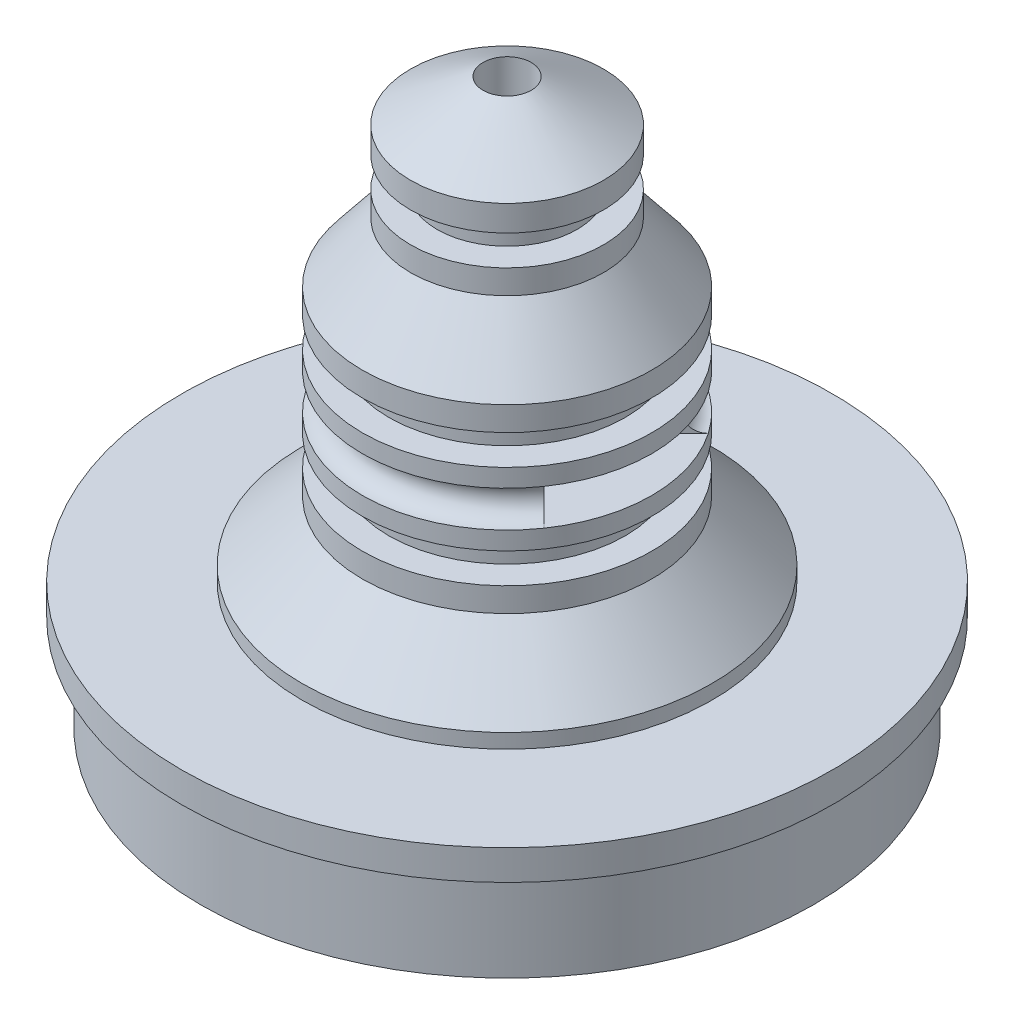
SolidWorks part; units mm, degrees
ref_plane "Спереди" through (0, 0, 0) normal (0, 0, 1) x (1, 0, 0)
ref_plane "Сверху" through (0, 0, 0) normal (0, 1, 0) x (1, 0, 0)
ref_plane "Справа" through (0, 0, 0) normal (1, 0, 0) x (0, 0, -1)
sketch "Эскиз1" plane through (0, 0, 0) normal (0, 0, 1) x (1, 0, 0)
  line L0 (0, 0) -> (0, 60) construction
  line L1 (17, 27) -> (17, 25.8)
  line L2 (2, 62.0979) -> (2, 15.3)
  line L6 (8, 56.5) -> (5.8, 56.5)
  line L7 (5.8, 56.5) -> (5.8, 54)
  line L8 (5.8, 54) -> (8, 54)
  line L10 (8, 58.6338) -> (8, 56.5)
  line L11 (8, 54) -> (8, 52)
  line L12 (8, 52) -> (12, 47)
  line L13 (12, 47) -> (12, 45)
  line L14 (12, 45) -> (9.8, 45)
  line L15 (9.8, 45) -> (9.8, 42.5)
  line L16 (9.8, 42.5) -> (12, 42.5)
  line L17 (12, 39.5) -> (9.0242, 39.5) construction
  line L18 (12, 42.5) -> (12, 41)
  line L19 (12, 36.5) -> (12, 38)
  line L20 (12, 34) -> (9.8, 34)
  line L21 (9.8, 34) -> (9.8, 36.5)
  line L22 (9.8, 36.5) -> (12, 36.5)
  line L23 (12, 34) -> (12, 32)
  line L24 (12, 32) -> (17, 27)
  line L29 (17, 25.8) -> (27, 25.8)
  line L33 (27, 25.8) -> (27, 23.3)
  line L34 (27, 23.3) -> (25.4, 23.3)
  line L35 (25.4, 23.3) -> (25.4, 15.3)
  line L36 (25.4, 15.3) -> (2, 15.3)
  line L37 (8, 58.6338) -> (2, 62.0979)
  arc A1 (12, 41) -> (12, 38) centre (12, 39.5) ccw
  point P22 (12, 41)
  dimension "D5" = 2.5
  dimension "D14" = 3
  dimension "D3" = 4
  dimension "D4" = 16
  dimension "D6" = 2
  dimension "D7" = 2.2
  dimension "D8" = 60
  dimension "D9" = 24
  dimension "D10" = 5
  dimension "D11" = 2.5
  dimension "D12" = 2.2
  dimension "D13" = 2
  dimension "D15" = 1.5
  dimension "D16" = 2
  dimension "D17" = 5
  dimension "D18" = 34
  dimension "D19" = 1.2
  dimension "D20" = 2.5
  dimension "D21" = 8
  dimension "D22" = 10
  dimension "D23" = 1.6
  dimension "D24" = 7.8
revolve "Повернуть1" add sketch "Эскиз1" angle 360 about L0 reverse direction yes
sketch "Эскиз3" plane through (0, 15.3, 0) normal (0, -1, 0) x (1, 0, 0)
  line L0 (50, 0) -> (-50, 0) construction
  circle A0 centre (5.9, 0) radius 2
  dimension "D1" = 4
  dimension "D2" = 5.9
ref_plane "Плоскость1" through (0, 41, 0) normal (0, -1, 0) x (-1, 0, 0)
extrude "Вырез-Вытянуть1" cut sketch "Эскиз3" against normal up to surface (25.7 mm away) up to plane "Плоскость1"
ref_plane "Плоскость2" through (0, 38, 0) normal (0, -1, 0) x (-1, 0, 0)
sketch "Эскиз4" plane through (0, 41, 0) normal (0, -1, 0) x (-1, 0, 0)
  line L0 (-4.4858, 1.4142) -> (-9.8809, 6.8094)
  line L1 (-5.9, 0) -> (-22.1819, 0) construction
  line L2 (-50, 0) -> (50, 0) construction
  line L3 (-4.4858, -1.4142) -> (-9.8809, -6.8094)
  circle A0 centre (0, 0) radius 12 construction
  arc A1 (-9.8809, 6.8094) -> (-9.8809, -6.8094) centre (0, 0) ccw
  circle A2 centre (-5.9, 0) radius 2 construction
  arc A3 (-4.4858, -1.4142) -> (-4.4858, 1.4142) centre (-5.9, 0) ccw
  dimension "D1" = 90
extrude "Вырез-Вытянуть2" cut sketch "Эскиз4" along normal up to surface (3 mm away) up to plane "Плоскость2"
